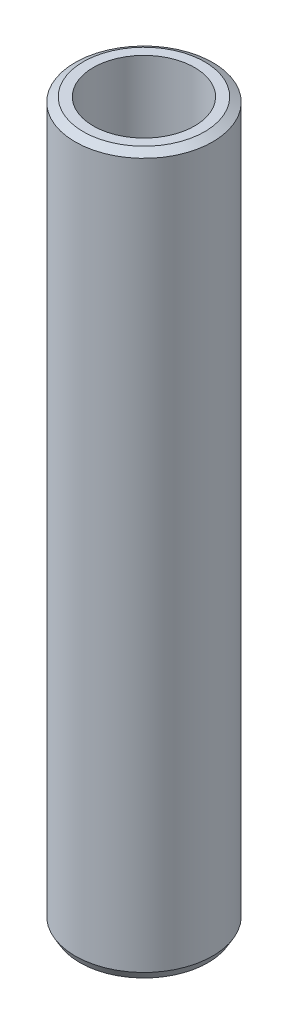
SolidWorks part; units mm, degrees
ref_plane "Front Plane" through (0, 0, 0) normal (0, 0, 1) x (1, 0, 0)
ref_plane "Top Plane" through (0, 0, 0) normal (0, 1, 0) x (1, 0, 0)
ref_plane "Right Plane" through (0, 0, 0) normal (1, 0, 0) x (0, 0, -1)
sketch "Sketch1" plane through (0, 0, 0) normal (0, 1, 0) x (1, 0, 0)
  circle A0 centre (0, 0) radius 57.5
  dimension "SHAFT_OD" = 115
extrude "Boss-Extrude1" add sketch "Sketch1" along normal blind 600
sketch "Sketch2" plane through (0, 0, 0) normal (0, 1, 0) x (1, 0, 0)
  circle A0 centre (0, 0) radius 42.3573
  dimension "BORE_D" = 84.7145
extrude "Cut-Extrude1" cut sketch "Sketch2" along normal through all
chamfer "Chamfer1" distance 3.9312 angle 60 2 edges at (0, 600, 57.5) (0, 0, 57.5) first distance on face at (0, 600, 57.5) first distance on face at (0, 0, 42.3573)
